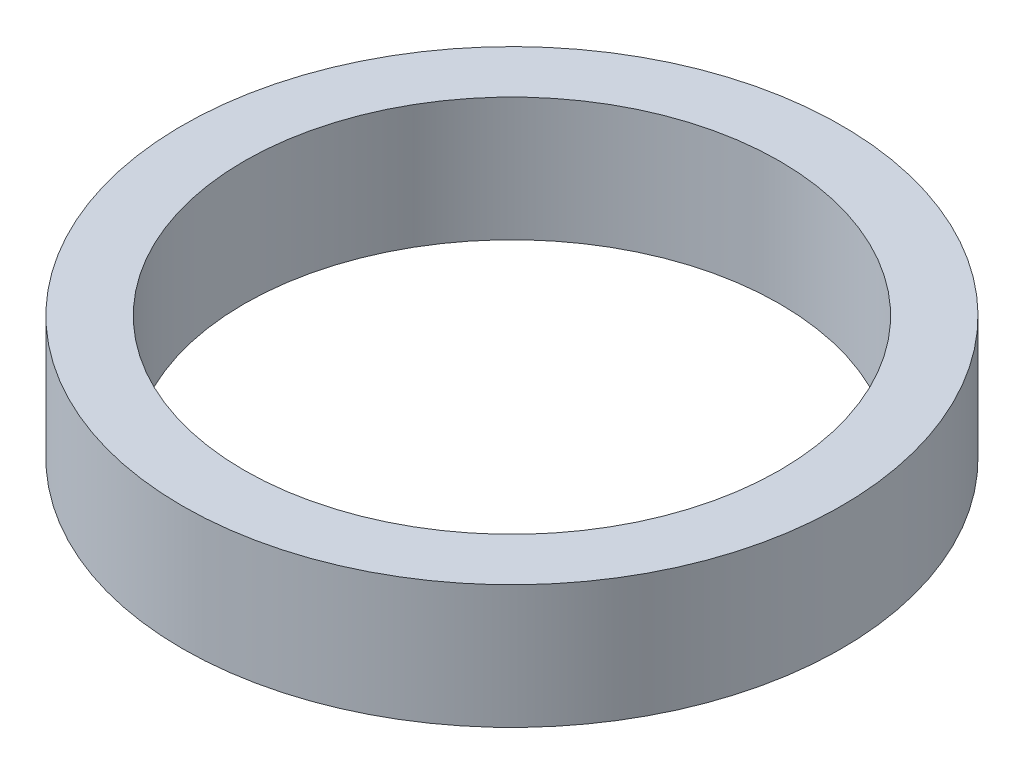
SolidWorks part; units mm, degrees
ref_plane "Front Plane" through (0, 0, 0) normal (0, 0, 1) x (1, 0, 0)
ref_plane "Top Plane" through (0, 0, 0) normal (0, 1, 0) x (1, 0, 0)
ref_plane "Right Plane" through (0, 0, 0) normal (1, 0, 0) x (0, 0, -1)
sketch "Sketch1" plane through (0, 0, 0) normal (0, 1, 0) x (1, 0, 0)
  circle A0 centre (0, 0) radius 40
  dimension "FLANGE_OD" = 80
extrude "Boss-Extrude1" add sketch "Sketch1" along normal blind 15
sketch "Sketch2" plane through (0, 0, 0) normal (0, 1, 0) x (1, 0, 0)
  circle A0 centre (0, 0) radius 32.5
  dimension "BORE_D" = 65
extrude "Cut-Extrude1" cut sketch "Sketch2" along normal through all
sketch "Sketch3" plane through (0, 15, 0) normal (0, 1, 0) x (1, 0, 0)
  circle A0 centre (0, 0) radius 17.8101 construction
  circle A1 centre (-17.8101, 0) radius 1.5
  dimension "BOLT_D" = 3
  dimension "BOLT_PCD" = 35.6201
extrude "Cut-Extrude2" cut sketch "Sketch3" against normal blind 14.766 rebuild error yes
pattern_circular "CirPattern1" count 4 over 360 rebuild error yes
